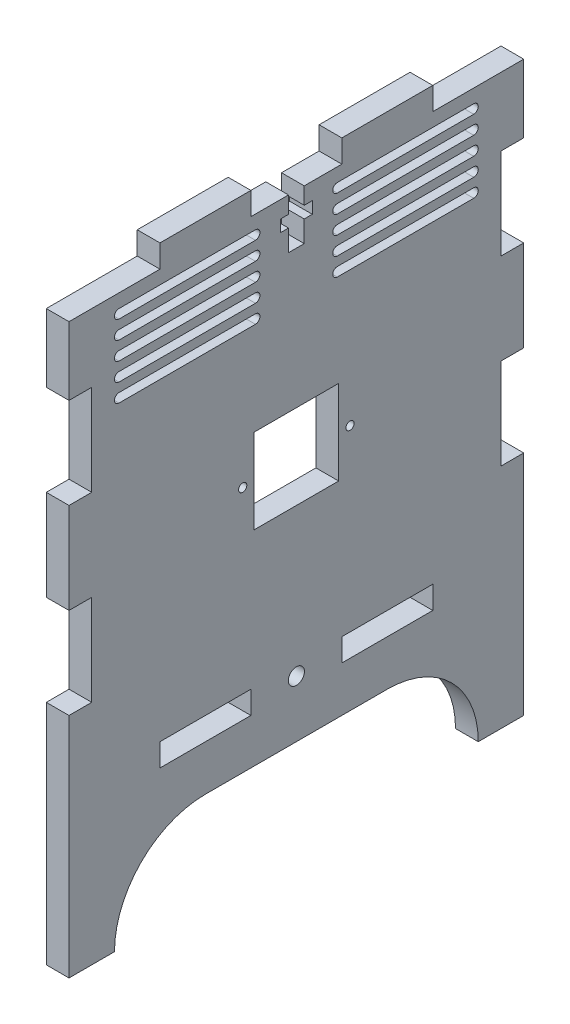
SolidWorks part; units mm, degrees
ref_plane "Front Plane" through (0, 0, 0) normal (0, 0, 1) x (1, 0, 0)
ref_plane "Top Plane" through (0, 0, 0) normal (0, 1, 0) x (1, 0, 0)
ref_plane "Right Plane" through (0, 0, 0) normal (1, 0, 0) x (0, 0, -1)
sketch "Sketch1" plane through (0, 0, 0) normal (1, 0, 0) x (0, 0, -1)
  line L1 (-63.5, 82.55) -> (63.5, 82.55)
  line L2 (-63.5, 82.55) -> (-63.5, -82.55)
  line L3 (-63.5, -82.55) -> (63.5, -82.55)
  line L4 (63.5, 82.55) -> (63.5, -82.55)
  line L5 (-63.5, 82.55) -> (63.5, -82.55) construction
  line L6 (-63.5, -82.55) -> (63.5, 82.55) construction
  point P0 (0, 0)
  dimension "D1" = 127
  dimension "D2" = 165.1
extrude "Boss-Extrude1" add sketch "Sketch1" along normal blind 6.35
sketch "Sketch2" plane through (6.35, 0, 0) normal (1, 0, 0) x (0, 0, -1)
  line L1 (-63.5, 82.55) -> (-38.1, 82.55)
  line L2 (-63.5, 82.55) -> (-63.5, 76.2)
  line L3 (-63.5, 76.2) -> (-38.1, 76.2)
  line L4 (-38.1, 82.55) -> (-38.1, 76.2)
  dimension "D1" = 25.4
  dimension "D2" = 6.35
extrude "Cut-Extrude1" cut sketch "Sketch2" against normal blind 6.35
pattern_linear "LPattern1" count 3 spacing 50.8 along (0, 0, -1) of "Cut-Extrude1"
sketch "Sketch5" plane through (6.35, 0, 0) normal (1, 0, 0) x (0, 0, -1)
  line L0 (-25.4, -82.55) -> (25.4, -82.55) construction
  line L1 (-63.5, -82.55) -> (63.5, -82.55) construction
  line L2 (-25.4, -57.15) -> (25.4, -57.15)
  line L3 (-25.4, -107.95) -> (25.4, -107.95)
  arc A0 (-25.4, -57.15) -> (-25.4, -107.95) centre (-25.4, -82.55) ccw
  arc A1 (25.4, -107.95) -> (25.4, -57.15) centre (25.4, -82.55) ccw
  point P4 (0, -82.55)
  dimension "D2" = 25.4
  dimension "D1" = 50.8
extrude "Cut-Extrude4" cut sketch "Sketch5" against normal blind 6.35
sketch "Sketch8" plane through (6.35, 0, 0) normal (1, 0, 0) x (0, 0, -1)
  line L0 (63.5, -82.55) -> (63.5, 76.2) construction
  line L1 (63.5, 57.15) -> (57.15, 57.15)
  line L2 (63.5, 57.15) -> (63.5, 31.75)
  line L3 (63.5, 31.75) -> (57.15, 31.75)
  line L4 (57.15, 57.15) -> (57.15, 31.75)
  line L5 (38.1, 82.55) -> (12.7, 82.55) construction
  dimension "D1" = 25.4
  dimension "D2" = 25.4
  dimension "D3" = 6.35
extrude "Cut-Extrude6" cut sketch "Sketch8" against normal blind 6.35
pattern_linear "LPattern4" count 2 spacing 50.8 along (0, -1, 0) of "Cut-Extrude6"
ref_plane "Plane1" through (0, 0, 0) normal (0, 0, 1) x (1, 0, 0)
mirror "Mirror1" about plane through (0, 0, 0) normal (0, 0, 1) of "LPattern4"
sketch "Sketch9" plane through (0, 0, 0) normal (-1, 0, 0) x (0, 0, 1)
  line L0 (-63.5, -82.55) -> (-63.5, -19.05) construction
  line L1 (-38.1, -38.1) -> (-12.7, -38.1)
  line L2 (-38.1, -38.1) -> (-38.1, -44.45)
  line L3 (-38.1, -44.45) -> (-12.7, -44.45)
  line L4 (-12.7, -38.1) -> (-12.7, -44.45)
  line L5 (-38.1, 82.55) -> (-12.7, 82.55) construction
  point P6 (-25.4, 82.55)
  dimension "D1" = 25.4
  dimension "D2" = 6.35
  dimension "D3" = 25.4
  dimension "D4" = 120.65
extrude "Cut-Extrude7" cut sketch "Sketch9" against normal blind 6.35
pattern_linear "LPattern6" count 2 spacing 50.8 along (0, 0, 1) of "Cut-Extrude7"
sketch "Sketch16" plane through (0, 0, 0) normal (-1, 0, 0) x (0, 0, 1)
  line L0 (12.7, 76.2) -> (-12.7, 76.2) construction
  line L1 (-2.1971, 76.2) -> (2.1971, 76.2)
  line L2 (-2.1971, 76.2) -> (-2.1971, 62.23)
  line L3 (-2.1971, 62.23) -> (2.1971, 62.23)
  line L4 (2.1971, 76.2) -> (2.1971, 62.23)
  line L5 (-12.7, 76.2) -> (-12.7, 82.55) construction
  line L7 (-4.445, 71.501) -> (4.445, 71.501)
  line L8 (-4.445, 71.501) -> (-4.445, 68.199)
  line L9 (-4.445, 68.199) -> (4.445, 68.199)
  line L10 (4.445, 71.501) -> (4.445, 68.199)
  point P6 (0, 62.23)
  point P13 (0, 71.501)
  point P14 (4.445, 69.85)
  dimension "D1" = 4.3942
  dimension "D2" = 13.97
  dimension "D3" = 12.7
  dimension "D4" = 3.302
  dimension "D5" = 8.89
  dimension "D6" = 12.7
  dimension "D7" = 6.35
extrude "Cut-Extrude14" cut sketch "Sketch16" against normal blind 6.35 contours L7 L10 L9 L8 | L1 L4 L3 L2
hole_wizard "#8 Clearance Hole1" positions "Sketch18" profile "Sketch17" hole size "#8" standard "ANSI Inch"
sketch "Sketch18" plane through (0, 0, 0) normal (-1, 0, 0) x (0, 0, 1)
  line L3 (-12.7, -44.45) -> (-12.7, -38.1) construction
  line L4 (38.1, -38.1) -> (12.7, -38.1) construction
  point P0 (0, -41.275)
  point P16 (-12.7, -41.275)
  dimension "D1" = 12.7
  dimension "D2" = 3.175
sketch "Sketch17" plane through (0, -41.275, 0) normal (0, 1, 0) x (0, 0, 1)
  line L0 (0, 0) -> (0, 11.5107)
  line L1 (0, 11.5107) -> (2.2479, 10.16)
  line L2 (2.2479, 10.16) -> (2.2479, 0)
  line L5 (2.2479, 0) -> (0, 0)
  line L10 (0, 11.5107) -> (-2.2479, 10.16) construction
  line L11 (0, -6.35) -> (0, 107.95) construction
  dimension "Hole Dia." = 4.4958
  dimension "Hole Depth" = 10.16
  dimension "Drill Angle" = 118
sketch "Sketch19" plane through (0, 0, 0) normal (-1, 0, 0) x (0, 0, 1)
  line L0 (-49.53, 71.12) -> (-11.43, 71.12) construction
  line L1 (-49.53, 72.39) -> (-11.43, 72.39)
  line L2 (-49.53, 69.85) -> (-11.43, 69.85)
  line L3 (-38.1, 82.55) -> (-38.1, 76.2) construction
  line L4 (-2.1971, 76.2) -> (-12.7, 76.2) construction
  arc A0 (-49.53, 72.39) -> (-49.53, 69.85) centre (-49.53, 71.12) ccw
  arc A1 (-11.43, 69.85) -> (-11.43, 72.39) centre (-11.43, 71.12) ccw
  point P2 (-30.48, 71.12)
  point P7 (-30.48, 72.39)
  dimension "D2" = 1.27
  dimension "D1" = 38.1
  dimension "D3" = 7.62
  dimension "D4" = 3.81
extrude "Cut-Extrude15" cut sketch "Sketch19" against normal blind 6.35
mirror "Mirror2" about plane through (0, 0, 0) normal (0, 0, 1) of "Cut-Extrude15"
pattern_linear "LPattern7" count 5 spacing 5.08 along (0, -1, 0) of "Mirror2"
sketch "Sketch20" plane through (0, 0, 0) normal (-1, 0, 0) x (0, 0, 1)
  line L0 (-63.5, 6.35) -> (-63.5, 31.75) construction
  line L1 (-11.811, 23.622) -> (11.811, 23.622)
  line L2 (-11.811, 23.622) -> (-11.811, 0)
  line L3 (-11.811, 0) -> (11.811, 0)
  line L4 (11.811, 23.622) -> (11.811, 0)
  line L5 (38.1, -38.1) -> (12.7, -38.1) construction
  circle A0 centre (-14.986, 11.811) radius 1.143
  circle A1 centre (14.986, 11.811) radius 1.143
  point P4 (0, 0)
  point P11 (0, 23.622)
  point P12 (-11.811, 11.811)
  point P15 (11.811, 11.811)
  dimension "D6" = 2.286
  dimension "D7" = 2.286
  dimension "D8" = 14.986
  dimension "D1" = 23.622
  dimension "D2" = 23.622
  dimension "D3" = 63.5
  dimension "D4" = 38.1
  dimension "D5" = 14.986
extrude "Cut-Extrude16" cut sketch "Sketch20" against normal blind 10.16
